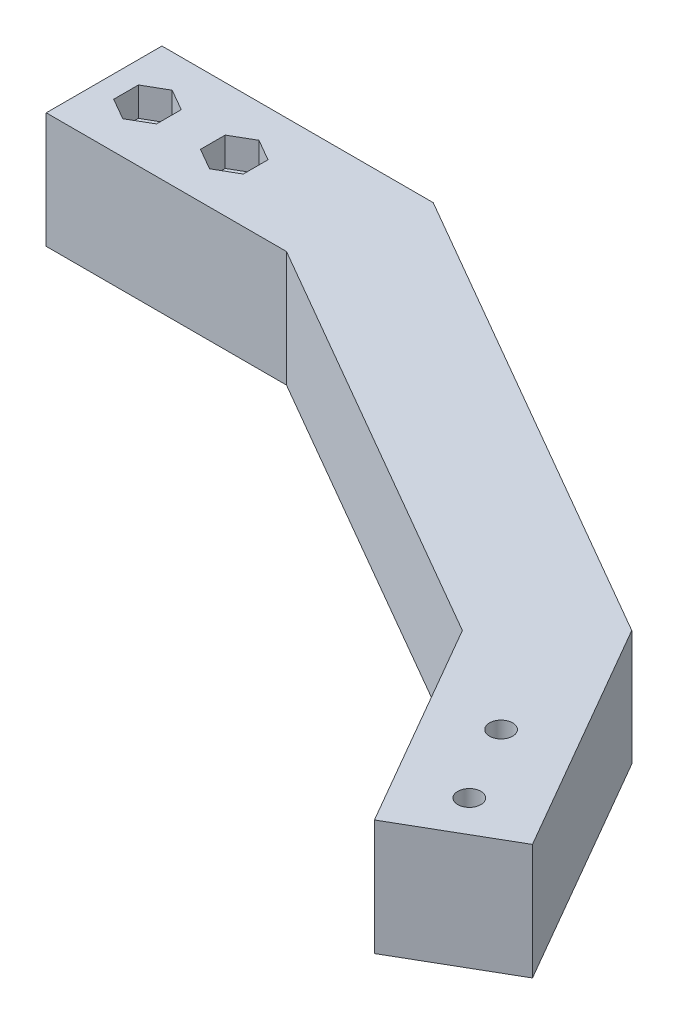
SolidWorks part; units mm, degrees
ref_plane "Front Plane" through (0, 0, 0) normal (0, 0, 1) x (1, 0, 0)
ref_plane "Top Plane" through (0, 0, 0) normal (0, 1, 0) x (1, 0, 0)
ref_plane "Right Plane" through (0, 0, 0) normal (1, 0, 0) x (0, 0, -1)
sketch "Sketch1" plane through (0, 0, 0) normal (0, 1, 0) x (1, 0, 0)
  line L0 (0, 155) -> (0, 175)
  line L1 (0, 175) -> (46.8911, 175)
  line L2 (46.8911, 175) -> (128.1089, 128.1089)
  line L3 (0, 0) -> (221.2337, 383.1881) construction
  line L4 (0, 155) -> (41.5321, 155)
  line L5 (41.5321, 155) -> (113.4679, 113.4679)
  line L6 (134.2339, 77.5) -> (113.4679, 113.4679)
  line L7 (151.5544, 87.5) -> (128.1089, 128.1089)
  line L8 (134.2339, 77.5) -> (151.5544, 87.5)
  line L9 (0, 155) -> (0, 150) construction
  circle A0 centre (0, 0) radius 150 construction
  dimension "D1" = 300
  dimension "D2" = 20
  dimension "D3" = 150
  dimension "D4" = 20
  dimension "D5" = 175
  dimension "D6" = 25
extrude "Boss-Extrude1" add sketch "Sketch1" along normal blind 20
sketch "Sketch2" plane through (0, 20, 0) normal (0, 1, 0) x (1, 0, 0)
  line L0 (87.5, 151.5544) -> (77.5, 134.2339) construction
  line L1 (128.1089, 128.1089) -> (46.8911, 175) construction
  line L2 (41.5321, 155) -> (113.4679, 113.4679) construction
  line L3 (41.5321, 155) -> (41.5321, 175) construction
  line L4 (7.5, 160.7276) -> (11.2, 162.8638)
  line L5 (11.2, 162.8638) -> (11.2, 167.1362)
  line L6 (11.2, 167.1362) -> (7.5, 169.2724)
  line L7 (7.5, 169.2724) -> (3.8, 167.1362)
  line L8 (3.8, 167.1362) -> (3.8, 162.8638)
  line L9 (3.8, 162.8638) -> (7.5, 160.7276)
  line L10 (46.8911, 175) -> (0, 175) construction
  line L11 (41.5321, 165) -> (0, 165) construction
  line L12 (0, 175) -> (0, 155) construction
  line L13 (122.1281, 118.4679) -> (142.8942, 82.5) construction
  line L14 (22.5, 169.2724) -> (18.8, 167.1362)
  line L15 (18.8, 167.1362) -> (18.8, 162.8638)
  line L16 (18.8, 162.8638) -> (22.5, 160.7276)
  line L17 (22.5, 160.7276) -> (26.2, 162.8638)
  line L18 (26.2, 162.8638) -> (26.2, 167.1362)
  line L19 (26.2, 167.1362) -> (22.5, 169.2724)
  line L20 (113.4679, 113.4679) -> (130.7884, 123.4679) construction
  line L21 (131.6442, 106.258) -> (135.3442, 104.1218)
  line L22 (127.9442, 104.1218) -> (131.6442, 106.258)
  line L23 (127.9442, 99.8494) -> (127.9442, 104.1218)
  line L24 (131.6442, 97.7132) -> (127.9442, 99.8494)
  line L25 (135.3442, 99.8494) -> (131.6442, 97.7132)
  line L26 (135.3442, 104.1218) -> (135.3442, 99.8494)
  line L27 (139.1442, 84.7228) -> (135.4442, 86.859)
  line L28 (142.8442, 86.859) -> (139.1442, 84.7228)
  line L29 (142.8442, 91.1314) -> (142.8442, 86.859)
  line L30 (139.1442, 93.2676) -> (142.8442, 91.1314)
  line L31 (135.4442, 91.1314) -> (139.1442, 93.2676)
  line L32 (135.4442, 86.859) -> (135.4442, 91.1314)
  circle A0 centre (7.5, 165) radius 3.7 construction
  circle A1 centre (22.5, 165) radius 3.7 construction
  circle A2 centre (7.5, 165) radius 2
  circle A3 centre (22.5, 165) radius 2
  circle A4 centre (131.6442, 101.9856) radius 3.7 construction
  circle A5 centre (139.1442, 88.9952) radius 3.7 construction
  circle A6 centre (131.6442, 101.9856) radius 2
  circle A7 centre (139.1442, 88.9952) radius 2
  dimension "D4" = 4
  dimension "D1" = 7.4
  dimension "D2" = 7.5
  dimension "D3" = 15
extrude "Cut-Extrude1" cut sketch "Sketch2" against normal through all contours A2 | A3 | A6 | A7 region at (7.5, 20, -165) region at (22.5, 20, -165) region at (131.6442, 20, -101.9856)
extrude "Cut-Extrude2" cut sketch "Sketch2<3>" against normal blind 5 contours L8 L9 L4 L5 L6 L7 A2 | L18 L19 L14 L15 L16 L17 A3 region at (5.7065, 20, -161.8936) region at (24.2935, 20, -168.1064)
sketch "Sketch2<3>" plane through (0, 20, 0) normal (0, 1, 0) x (1, 0, 0) same geometry as "Sketch2"
extrude "Cut-Extrude3" cut sketch "Sketch2<4>" along normal blind 5 from surface contours L26 L21 L22 L23 L24 L25 A6 | L32 L27 L28 L29 L30 L31 A7 region at (133.4377, 20, -105.092) region at (137.3507, 20, -85.8888) starting at face at (22.5, 0, -163)
sketch "Sketch2<4>" plane through (0, 20, 0) normal (0, 1, 0) x (1, 0, 0) same geometry as "Sketch2"
